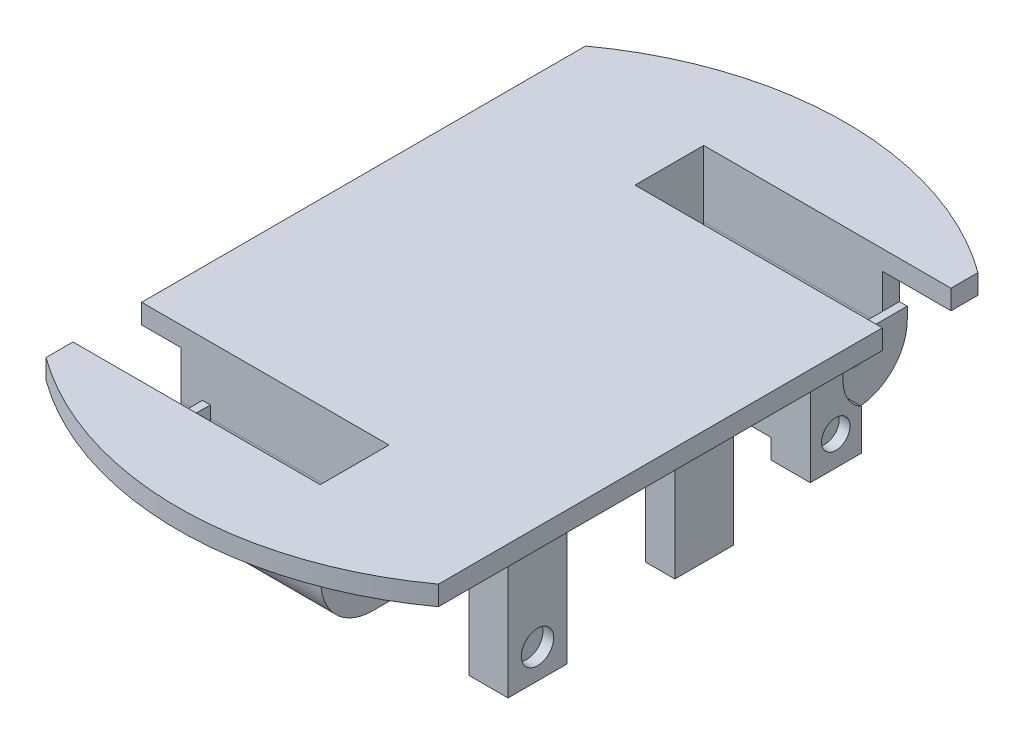
SolidWorks part; units mm, degrees
ref_plane "Front Plane" through (0, 0, 0) normal (0, 0, 1) x (1, 0, 0)
ref_plane "Top Plane" through (0, 0, 0) normal (0, 1, 0) x (1, 0, 0)
ref_plane "Right Plane" through (0, 0, 0) normal (1, 0, 0) x (0, 0, -1)
ref_axis "Center Axis" through (0, -34.25, 0) along (0, 1, 0)
sketch "Sketch1" plane through (0, 0, 0) normal (0, 1, 0) x (1, 0, 0)
  line L0 (-162.8746, 0) -> (178.0274, 0) construction
  line L1 (0, 86.4738) -> (0, -92.198) construction
  line L2 (-50, 68.7386) -> (-50, -68.7386)
  line L3 (50, 68.7386) -> (50, -68.7386)
  arc A0 (-50, 68.7386) -> (50, 68.7386) centre (0, 0) cw
  arc A1 (-50, -68.7386) -> (50, -68.7386) centre (0, 0) ccw
  dimension "D2" = 85
  dimension "D1" = 100
extrude "Base" add sketch "Sketch1" along normal blind 2.5 and the other way blind 2.5
sketch "Sketch2" plane through (0, -2.5, 0) normal (0, -1, 0) x (-1, 0, 0)
  line L0 (-133.3964, 0) -> (110.1594, 0) construction
  line L2 (41.5, -7.5) -> (49, -7.5)
  line L3 (41.5, -7.5) -> (41.5, 7.5)
  line L4 (41.5, 7.5) -> (49, 7.5)
  line L5 (49, -7.5) -> (49, 7.5)
  line L6 (0, -175.8738) -> (0, 153.5398) construction
  line L7 (7.5, -43.5) -> (-7.5, -43.5)
  line L8 (7.5, -43.5) -> (7.5, -36)
  line L9 (7.5, -36) -> (-7.5, -36)
  line L10 (-7.5, -43.5) -> (-7.5, -36)
  line L11 (-41.5, -7.5) -> (-49, -7.5)
  line L12 (-41.5, -7.5) -> (-41.5, 7.5)
  line L13 (-41.5, 7.5) -> (-49, 7.5)
  line L14 (-49, -7.5) -> (-49, 7.5)
  line L15 (7.5, 36) -> (-7.5, 36)
  line L16 (7.5, 36) -> (7.5, 43.5)
  line L17 (7.5, 43.5) -> (-7.5, 43.5)
  line L18 (-7.5, 36) -> (-7.5, 43.5)
  dimension "D1" = 15
  dimension "D2" = 7.5
  dimension "D3" = 36
  dimension "D4" = 41.5
  dimension "D5" = 41.5
  dimension "D6" = 36
  dimension "D7" = 7.5
  dimension "D8" = 7.5
  dimension "D9" = 7.5
  dimension "D10" = 15
  dimension "D11" = 15
  dimension "D12" = 15
extrude "BatteryHolder" add sketch "Sketch2" along normal blind 25
sketch "Sketch3" plane through (0, -27.5, 0) normal (0, -1, 0) x (-1, 0, 0)
  circle A0 centre (45.5, 0) radius 1.625
  circle A1 centre (0, -40) radius 1.625
  circle A2 centre (-45.5, 0) radius 1.625
  circle A3 centre (0, 40) radius 1.625
  dimension "D1" = 3.25
  dimension "D2" = 3.25
  dimension "D3" = 3.25
  dimension "D4" = 3.25
  dimension "D5" = 40
  dimension "D6" = 40
  dimension "D7" = 45.5
  dimension "D8" = 45.5
extrude "Cut-Extrude1" cut sketch "Sketch3" against normal blind 10
sketch "Sketch5" plane through (0, -2.5, 0) normal (0, -1, 0) x (-1, 0, 0)
  line L0 (-7.5, 36) -> (7.5, 36) construction
  line L1 (40, -49) -> (30, -49)
  line L2 (40, -49) -> (40, -36)
  line L3 (40, -36) -> (30, -36)
  line L4 (30, -49) -> (30, -36)
  line L5 (-30, 36) -> (-40, 36)
  line L6 (-30, 36) -> (-30, 49)
  line L7 (-30, 49) -> (-40, 49)
  line L8 (-40, 36) -> (-40, 49)
  line L9 (7.5, -36) -> (-7.5, -36) construction
  line L10 (-130.245, 42.5) -> (155.6892, 42.5) construction
  line L12 (155.6892, -42.5) -> (-162.2503, -42.5) construction
  line L14 (-162.2503, 0) -> (191.3178, 0) construction
  dimension "D1" = 85
  dimension "D2" = 30
  dimension "D3" = 30
  dimension "D4" = 10
  dimension "D5" = 10
extrude "Boss-Extrude2" add sketch "Sketch5" along normal blind 30
sketch "Sketch6" plane through (-40, 0, 0) normal (-1, 0, 0) x (0, 0, 1)
  line L0 (42.5, -32.5) -> (42.5, -2.5) construction
  line L2 (49, -2.5) -> (36, -2.5) construction
  line L4 (36, -32.5) -> (36, -2.5) construction
  line L5 (49, -32.5) -> (49, -2.5) construction
  circle A0 centre (42.5, -25) radius 3.625
  dimension "D1" = 7.25
  dimension "D2" = 22.5
extrude "Cut-Extrude2" cut sketch "Sketch6" against normal blind 2.75
sketch "Sketch7" plane through (40, 0, 0) normal (1, 0, 0) x (0, 0, -1)
  line L0 (42.5, -32.5) -> (42.5, -2.5) construction
  line L1 (49, -32.5) -> (36, -32.5) construction
  line L2 (49, -2.5) -> (36, -2.5) construction
  circle A0 centre (42.5, -25) radius 3.625
  dimension "D2" = 7.25
  dimension "D1" = 22.5
extrude "Cut-Extrude3" cut sketch "Sketch7" against normal blind 2.75
sketch "Sketch12" plane through (0, -2.5, 0) normal (0, -1, 0) x (-1, 0, 0)
  line L0 (30, -49) -> (32.5, -49)
  line L1 (30, -49) -> (40, -49) construction
  line L2 (32.5, -49) -> (32.5, -68.5)
  line L3 (-17.5, -68.5) -> (32.5, -68.5)
  line L5 (30, -36) -> (30, -49) construction
  line L8 (30, -36) -> (30, -49)
  line L9 (7.5, -43.5) -> (7.5, -36) construction
  line L10 (-7.5, -43.5) -> (7.5, -43.5) construction
  line L11 (-7.5, -36) -> (-7.5, -43.5) construction
  line L12 (7.5, -43.5) -> (7.5, -36)
  line L13 (-7.5, -43.5) -> (7.5, -43.5)
  line L14 (-7.5, -36) -> (-7.5, -43.5)
  line L15 (7.5, -36) -> (30, -36)
  line L16 (-7.5, -36) -> (-17.5, -36)
  line L17 (-17.5, -36) -> (-17.5, -68.5)
  dimension "D1" = 32.5
  dimension "D2" = 10
  dimension "D3" = 2.5
extrude "Boss-Extrude4" add sketch "Sketch12" along normal up to surface (25 mm away) up to face at (0, -27.5, 38.375)
sketch "Sketch11" plane through (0, 0, 0) normal (1, 0, 0) x (0, 0, -1)
  line L0 (-44.3566, -14.3934) -> (-44.3566, 2.5)
  line L2 (-44.3566, 2.5) -> (-61.8566, 2.5)
  line L3 (-61.8566, 2.5) -> (-61.8566, -14.3934)
  line L5 (-39.2149, -28.2851) -> (-65.2384, -2.2616) construction
  line L7 (-68.7386, 2.5) -> (-85, 2.5) construction
  line L8 (0, 86.9309) -> (0, -106.9577) construction
  arc A0 (-61.8566, -14.3934) -> (-44.3566, -14.3934) centre (-53.1066, -14.3934) ccw
  circle A2 centre (-42.5, -25) radius 3.625 construction
  circle A3 centre (-42.5, -25) radius 3.625 construction
  dimension "D3" = 8.75
  dimension "D1" = 15
  dimension "D2" = 45
extrude "Cut-Extrude6" cut sketch "Sketch11" against normal blind 50 and the other way blind 13
sketch "Sketch13" plane through (-32.5, 0, 0) normal (-1, 0, 0) x (0, 0, 1)
  line L4 (68.5, -27.5) -> (49, -27.5) construction
  line L5 (66.2132, -14.3934) -> (66.2132, -2.5)
  line L8 (66.2132, -2.5) -> (68.5, -2.5)
  line L9 (68.5, -2.5) -> (61.8566, -2.5) construction
  line L10 (68.5, -2.5) -> (68.5, -27.5)
  line L11 (68.5, -27.5) -> (53.1066, -27.5)
  arc A0 (53.1066, -27.5) -> (66.2132, -14.3934) centre (53.1066, -14.3934) ccw
  point P5 (0, 0)
extrude "Cut-Extrude7" cut sketch "Sketch13" against normal up to next
sketch "Sketch14" plane through (-32.5, 0, 0) normal (-1, 0, 0) x (0, 0, 1)
  line L0 (53.1066, -27.5) -> (49, -27.5) construction
  line L1 (66.2132, -2.5) -> (66.2132, -14.3934) construction
  line L2 (49, -27.5) -> (49, -22.1199)
  line L3 (44.3566, -11.3934) -> (49.3566, -11.3934)
  line L4 (49.3566, -11.3934) -> (49.3566, -14.3934)
  line L5 (56.8566, -14.3934) -> (56.8566, -11.3934)
  line L6 (56.8566, -11.3934) -> (66.2132, -11.3934)
  line L7 (66.2132, -11.3934) -> (66.2132, -14.3934)
  line L9 (44.3566, -14.3934) -> (44.3566, -11.3934)
  line L10 (49, -27.5) -> (53.1066, -27.5)
  arc A0 (49.3566, -14.3934) -> (56.8566, -14.3934) centre (53.1066, -14.3934) ccw
  arc A1 (66.2132, -14.3934) -> (53.1066, -27.5) centre (53.1066, -14.3934) cw
  arc A2 (53.1066, -27.5) -> (66.2132, -14.3934) centre (53.1066, -14.3934) ccw construction
  arc A3 (49, -22.1199) -> (61.8566, -14.3934) centre (53.1066, -14.3934) ccw construction
  arc A4 (44.3566, -14.3934) -> (61.8566, -14.3934) centre (53.1066, -14.3934) ccw construction
  arc A6 (49, -22.1199) -> (44.3566, -14.3934) centre (53.1066, -14.3934) cw
  arc A7 (44.3566, -14.3934) -> (49, -22.1199) centre (53.1066, -14.3934) ccw construction
  dimension "D1" = 3
  dimension "D2" = 7.5
extrude "Boss-Extrude5" add sketch "Sketch14" along normal blind 2
sketch "Sketch15" plane through (-34.5, 0, 0) normal (-1, 0, 0) x (0, 0, 1)
  line L0 (47.6066, -14.3934) -> (58.6066, -14.3934) construction
  circle A0 centre (58.6066, -14.3934) radius 0.875
  circle A1 centre (47.6066, -14.3934) radius 0.875
  arc A2 (49.3566, -14.3934) -> (56.8566, -14.3934) centre (53.1066, -14.3934) ccw construction
  arc A3 (49.3566, -14.3934) -> (56.8566, -14.3934) centre (53.1066, -14.3934) ccw construction
  dimension "D1" = 1.75
  dimension "D2" = 1.75
  dimension "D3" = 11
extrude "Cut-Extrude8" cut sketch "Sketch15" against normal up to next
sketch "Sketch16" plane through (0, 0, 36) normal (0, 0, -1) x (-1, 0, 0)
  line L0 (0, 14.1041) -> (0, -56.6149) construction
  line L1 (3, -25.5) -> (-3, -25.5)
  line L2 (3, -25.5) -> (3, -23)
  line L3 (3, -23) -> (-3, -23)
  line L4 (-3, -25.5) -> (-3, -23)
  line L5 (7.5, -27.5) -> (-7.5, -27.5) construction
  dimension "D1" = 2
  dimension "D2" = 6
  dimension "D3" = 2.5
extrude "NutCut" cut sketch "Sketch16" against normal blind 10
sketch "Sketch17" plane through (0, -2.5, 0) normal (0, -1, 0) x (-1, 0, 0)
  line L0 (-49, 7.5) -> (-49, -7.5) construction
  line L1 (-49, -50) -> (-39, -50)
  line L2 (-49, -50) -> (-49, -35)
  line L3 (-49, -35) -> (-39, -35)
  line L4 (-39, -50) -> (-39, -35)
  line L5 (-121.7994, -42.5) -> (-23.7999, -42.5) construction
  dimension "D1" = 42.5
  dimension "D2" = 15
  dimension "D3" = 10
extrude "Boss-Extrude6" add sketch "Sketch17" along normal blind 30
sketch "Sketch18" plane through (49, 0, 0) normal (1, 0, 0) x (0, 0, -1)
  line L0 (-42.5, -7.6315) -> (-42.5, -33.0073) construction
  line L1 (-35, -32.5) -> (-35, -2.5) construction
  line L2 (-50, -32.5) -> (-50, -2.5) construction
  line L4 (68.7386, -2.5) -> (-44.3566, -2.5) construction
  circle A0 centre (-42.5, -25) radius 4.125
  dimension "D1" = 8.25
  dimension "D2" = 22.5
extrude "Cut-Extrude11" cut sketch "Sketch18" against normal blind 2.75
pattern_circular "CirPattern2" count 2 over 360 about axis through (0, -34.25, 0) along (0, 1, 0) of "Boss-Extrude4", "Cut-Extrude6", "Cut-Extrude7", "Boss-Extrude5", "Cut-Extrude8"
